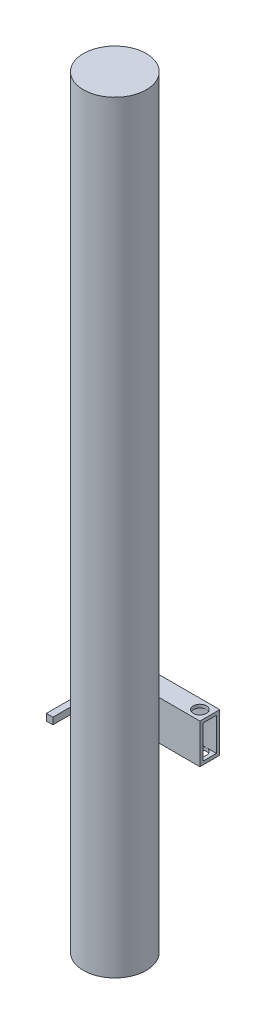
SolidWorks part; units mm, degrees
ref_plane "Front Plane" through (0, 0, 0) normal (0, 0, 1) x (1, 0, 0)
ref_plane "Top Plane" through (0, 0, 0) normal (0, 1, 0) x (1, 0, 0)
ref_plane "Right Plane" through (0, 0, 0) normal (1, 0, 0) x (0, 0, -1)
sketch "Elevation Bar" plane through (0, 0, 0) normal (0, 1, 0) x (1, 0, 0)
  circle A0 centre (0, 0) radius 30.226
  dimension "D1" = 60.452
extrude "Elevation Bar Part" add sketch "Elevation Bar" along normal blind 734.06
sketch "Pole and Drivetrain Pos" plane through (0, 0, 0) normal (0, 0, 1) x (1, 0, 0)
  line L0 (0, 0) -> (172.1794, 0) construction
  line L1 (-30.226, 0) -> (-30.226, 734.06) construction
  line L2 (-30.226, 734.06) -> (30.226, 734.06) construction
  line L3 (30.226, 734.06) -> (30.226, 0) construction
  line L4 (30.226, 0) -> (30.226, 734.06) construction
  line L5 (636.651, 40.7185) -> (27.051, 40.7185) construction
  line L6 (636.651, 53.4185) -> (27.051, 53.4185)
  line L7 (636.651, 53.4185) -> (636.651, 28.0185)
  line L8 (636.651, 28.0185) -> (27.051, 28.0185)
  line L9 (27.051, 53.4185) -> (27.051, 28.0185)
  line L10 (-30.226, 93.98) -> (30.226, 93.98) construction
  line L11 (33.2486, 0) -> (-33.2486, 0) construction
  line L12 (30.226, 185.42) -> (-30.226, 185.42) construction
  line L13 (30.226, 276.86) -> (-30.226, 276.86) construction
  line L14 (30.226, 368.3) -> (-30.226, 368.3) construction
  line L15 (30.226, 459.74) -> (-30.226, 459.74) construction
  line L16 (30.226, 551.18) -> (-30.226, 551.18) construction
  line L17 (30.226, 642.62) -> (-30.226, 642.62) construction
  line L18 (30.226, 73.152) -> (750.8896, 73.152) construction
  circle A0 centre (576.5632, 40.7185) radius 41.275 construction
  circle A1 centre (87.1388, 40.7185) radius 41.275 construction
  circle A2 centre (331.851, 40.7185) radius 41.275 construction
  point P24 (331.851, 40.7185)
  dimension "D2" = 82.55
  dimension "D1" = 609.6
  dimension "D3" = 25.4
  dimension "D4" = 244.7122
  dimension "D5" = 244.7122
  dimension "D6" = 93.98
  dimension "D7" = 185.42
  dimension "D8" = 276.86
  dimension "D9" = 368.3
  dimension "D10" = 459.74
  dimension "D11" = 551.18
  dimension "D12" = 642.62
  dimension "D13" = 73.152
sketch "Driving Wheels Geo" plane through (0, 0, 0) normal (0, 0, 1) x (1, 0, 0)
  line L0 (-30.226, 182.88) -> (-30.226, 101.727) construction
  line L1 (55.626, 101.727) -> (30.226, 101.727) construction
  line L2 (-30.226, 0) -> (-30.226, 734.06) construction
  line L3 (30.226, 734.06) -> (30.226, 0) construction
  line L5 (30.226, 101.727) -> (-30.226, 101.727) construction
  line L6 (-30.226, 182.88) -> (30.226, 101.727) construction
  line L7 (31.8135, 101.727) -> (-30.226, 182.88) construction
  line L8 (30.226, 226.8605) -> (203.668, 53.4185) construction
  line L9 (-55.626, 208.28) -> (31.6164, 208.28) construction
  line L10 (30.226, 73.152) -> (750.8896, 73.152) construction
  line L11 (636.651, 53.4185) -> (27.051, 53.4185) construction
  line L14 (-55.626, 157.48) -> (31.6164, 157.48) construction
  line L15 (31.6164, 157.48) -> (31.6164, 208.28) construction
  line L17 (18.9164, 208.28) -> (44.3164, 208.28) construction
  line L18 (18.9164, 208.28) -> (18.9164, 157.48) construction
  line L19 (18.9164, 157.48) -> (44.3164, 157.48) construction
  line L20 (44.3164, 208.28) -> (44.3164, 157.48) construction
  line L21 (18.9164, 208.28) -> (44.3164, 157.48) construction
  line L22 (18.9164, 157.48) -> (44.3164, 208.28) construction
  circle A1 centre (55.626, 101.727) radius 25.4
  circle A3 centre (-55.626, 182.88) radius 25.4
  circle A4 centre (81.026, 104.2185) radius 50.8 construction
  circle A5 centre (55.626, 101.727) radius 23.8125 construction
  point P28 (31.6164, 182.88)
  dimension "D1" = 50.8
  dimension "D2" = 1.5875
  dimension "D3" = 52.603
  dimension "D4" = 3.175
  dimension "D5" = 182.88
  dimension "D8" = 101.6
  dimension "D6" = 50.8
  dimension "D13" = 3.175
  dimension "D7" = 81.153
  dimension "D9" = 45
  dimension "D10" = 53.317
  dimension "D11" = 25.4
  dimension "D12" = 48.3085
ref_plane "Plane1" through (0, 182.88, 0) normal (0, 1, 0) x (1, 0, 0)
sketch "Clamp Geo" plane through (0, 182.88, 0) normal (0, 1, 0) x (1, 0, 0)
  line L0 (-42.926, -19.8438) -> (-42.926, 50.8635) construction
  line L3 (27.051, 228.6) -> (27.051, -228.6) construction
  line L4 (50.0464, 31.8135) -> (-49.276, 31.8135)
  line L5 (50.0464, 31.8135) -> (50.0464, 50.8635)
  line L6 (50.0464, 50.8635) -> (-49.276, 50.8635)
  line L7 (-49.276, 31.8135) -> (-49.276, 50.8635)
  line L10 (-46.101, 50.8635) -> (-39.751, 50.8635)
  line L11 (-46.101, 50.8635) -> (-46.101, -19.8438)
  line L12 (-46.101, -19.8438) -> (-39.751, -19.8438)
  line L13 (-39.751, 50.8635) -> (-39.751, -19.8438)
  line L14 (-55.626, 12.7) -> (-30.226, 12.7) construction
  line L15 (-55.626, 12.7) -> (-55.626, -12.7) construction
  line L16 (-55.626, -12.7) -> (-30.226, -12.7) construction
  line L17 (-30.226, 12.7) -> (-30.226, -12.7) construction
  line L18 (-55.626, 12.7) -> (-30.226, -12.7) construction
  line L19 (-55.626, -12.7) -> (-30.226, 12.7) construction
  line L20 (0, -30.226) -> (0, 30.226) construction
  line L21 (-30.226, 0) -> (30.226, 0) construction
  line L22 (-46.101, 46.101) -> (-42.926, 46.101) construction
  line L23 (-39.751, 41.3385) -> (-46.101, 41.3385)
  line L24 (-46.101, 41.3385) -> (-46.101, 50.8635) construction
  line L25 (-39.751, 31.8135) -> (-39.751, 50.8635) construction
  line L26 (50.0464, 41.3385) -> (40.5214, 41.3385) construction
  circle A0 centre (0, 0) radius 30.226 construction
  circle A3 centre (-42.926, 46.101) radius 1.8288
  circle A5 centre (-42.926, 36.576) radius 1.8288
  circle A6 centre (40.5214, 41.3385) radius 6.35
  circle A7 centre (40.5214, 41.3385) radius 13.4704 construction
  point P14 (-42.926, 0)
  point P32 (-39.751, 41.3385)
  point P34 (-46.101, 41.3385)
  point P36 (-42.926, 41.3385)
  point P42 (50.0464, 41.3385)
  dimension "D1" = 60.452
  dimension "D4" = 1.5875
  dimension "D7" = 3.6576
  dimension "D8" = 3.175
  dimension "D10" = 12.7
  dimension "D11" = 3.175
  dimension "D2" = 457.2
  dimension "D3" = 19.05
  dimension "D5" = 6.35
  dimension "D6" = 25.4
  dimension "D9" = 99.3224
  dimension "D13" = 7.1437
sketch "Locked Setting Geo" plane through (0, 182.88, 0) normal (0, 1, 0) x (1, 0, 0)
  line L0 (30.2525, 144.301) -> (91.1428, 108.3583) construction
  line L1 (27.477, 37.9778) -> (77.9656, 123.5104)
  line L2 (27.477, 37.9778) -> (43.8821, 28.2941)
  line L3 (43.8821, 28.2941) -> (94.3707, 113.8267)
  line L4 (77.9656, 123.5104) -> (94.3707, 113.8267)
  line L5 (92.7568, 111.0925) -> (89.5289, 105.6242)
  line L6 (92.7568, 111.0925) -> (31.8664, 147.0352)
  line L7 (31.8664, 147.0352) -> (28.6385, 141.5668)
  line L8 (89.5289, 105.6242) -> (28.6385, 141.5668)
  line L9 (64.7337, 138.6948) -> (51.8221, 116.8213) construction
  line L10 (64.7337, 138.6948) -> (42.8602, 151.6064) construction
  line L11 (42.8602, 151.6064) -> (29.9486, 129.7329) construction
  line L12 (51.8221, 116.8213) -> (29.9486, 129.7329) construction
  line L13 (64.7337, 138.6948) -> (29.9486, 129.7329) construction
  line L14 (42.8602, 151.6064) -> (51.8221, 116.8213) construction
  line L17 (88.6555, 113.5135) -> (87.0416, 110.7793) construction
  line L18 (81.3263, 110.466) -> (84.5542, 115.9344)
  line L19 (84.5542, 115.9344) -> (92.7568, 111.0925) construction
  line L20 (73.1238, 115.3079) -> (89.5289, 105.6242) construction
  line L21 (35.6795, 33.1359) -> (40.5214, 41.3385) construction
  line L22 (50.0464, 50.8635) -> (-49.276, 50.8635) construction
  line L23 (-46.101, 50.8635) -> (-46.101, -19.8438) construction
  line L24 (27.051, 228.6) -> (27.051, -228.6) construction
  circle A1 centre (87.0416, 110.7793) radius 1.8288
  circle A2 centre (78.839, 115.6211) radius 1.8288
  circle A3 centre (40.5214, 41.3385) radius 6.35
  point P10 (47.3411, 134.2138)
  point P28 (81.3263, 110.466)
  point P30 (84.5542, 115.9344)
  point P32 (82.9403, 113.2002)
  point P36 (35.6795, 33.1359)
  point P40 (40.5214, 41.3385)
  point P44 (-17.1792, 28.8062)
  dimension "D6" = 3.6576
  dimension "D9" = 12.7
  dimension "D2" = 19.05
  dimension "D3" = 1.5875
  dimension "D4" = 6.35
  dimension "D5" = 25.4
  dimension "D7" = 3.175
  dimension "D8" = 99.3224
  dimension "D10" = 3.175
  dimension "D11" = 50.8635
  dimension "D12" = 67.3197
extrude "Boss-Extrude1" add sketch "Clamp Geo" along normal blind 19.05 and the other way blind 19.05 separate body contours L6 L13 L4 L5 A6 | L11 L6 L7 L4 | L13 L23 L11 L4 A5 | L23 L13 L6 L11 A3 region at (2.3187, 182.88, -41.3385) region at (-42.926, 182.88, -31.928) region at (-47.6885, 182.88, -41.3385) region at (-42.926, 182.88, -41.453)
sketch "Sketch2" plane through (-49.276, 0, 0) normal (-1, 0, 0) x (0, 0, 1)
  line L0 (-41.3385, 201.93) -> (-41.3385, 163.83) construction
  line L1 (-31.8135, 201.93) -> (-50.8635, 201.93) construction
  line L2 (-31.8135, 163.83) -> (-50.8635, 163.83) construction
  line L3 (-31.8135, 163.83) -> (-31.8135, 201.93) construction
  line L4 (-47.6885, 167.005) -> (-34.9885, 167.005)
  line L5 (-47.6885, 167.005) -> (-47.6885, 198.755)
  line L6 (-47.6885, 198.755) -> (-34.9885, 198.755)
  line L7 (-34.9885, 167.005) -> (-34.9885, 198.755)
  line L8 (-47.6885, 167.005) -> (-34.9885, 198.755) construction
  line L9 (-47.6885, 198.755) -> (-34.9885, 167.005) construction
  point P6 (-41.3385, 182.88)
  dimension "D1" = 3.175
  dimension "D2" = 3.175
extrude "Cut-Extrude2" cut sketch "Sketch2" against normal up to surface (99.3224 mm away) up to face at (50.0464, 182.88, -41.3385)
sketch "Sketch3" plane through (0, 0, -50.8635) normal (0, 0, -1) x (-1, 0, 0)
  line L2 (39.7129, 179.6669) -> (46.1391, 179.6669)
  line L3 (39.7129, 179.6669) -> (39.7129, 186.0931)
  line L4 (39.7129, 186.0931) -> (46.1391, 186.0931)
  line L5 (46.1391, 179.6669) -> (46.1391, 186.0931)
  line L6 (39.7129, 179.6669) -> (46.1391, 186.0931) construction
  line L7 (39.7129, 186.0931) -> (46.1391, 179.6669) construction
  point P0 (42.926, 182.88)
  point P1 (42.926, 182.88)
  dimension "D1" = 6.4262
extrude "Cut-Extrude3" cut sketch "Sketch3" against normal up to surface (19.05 mm away) up to face at (0.3852, 182.88, -31.8135)
extrude "Boss-Extrude2" add sketch "Clamp Geo<3>" along normal blind 3.175 and the other way blind 3.175 separate body contours L13 L4 L11 L12 | L13 L23 L11 L4 A5 | L23 L13 L6 L11 A3 region at (-42.926, 182.88, -5.9849) region at (-42.926, 182.88, -31.928) region at (-42.926, 182.88, -41.453)
sketch "Clamp Geo<3>" plane through (0, 182.88, 0) normal (0, 1, 0) x (1, 0, 0) same geometry as "Clamp Geo"
equation "\"D5@Pole and Drivetrain Pos\" = \"D4@Pole and Drivetrain Pos\""
